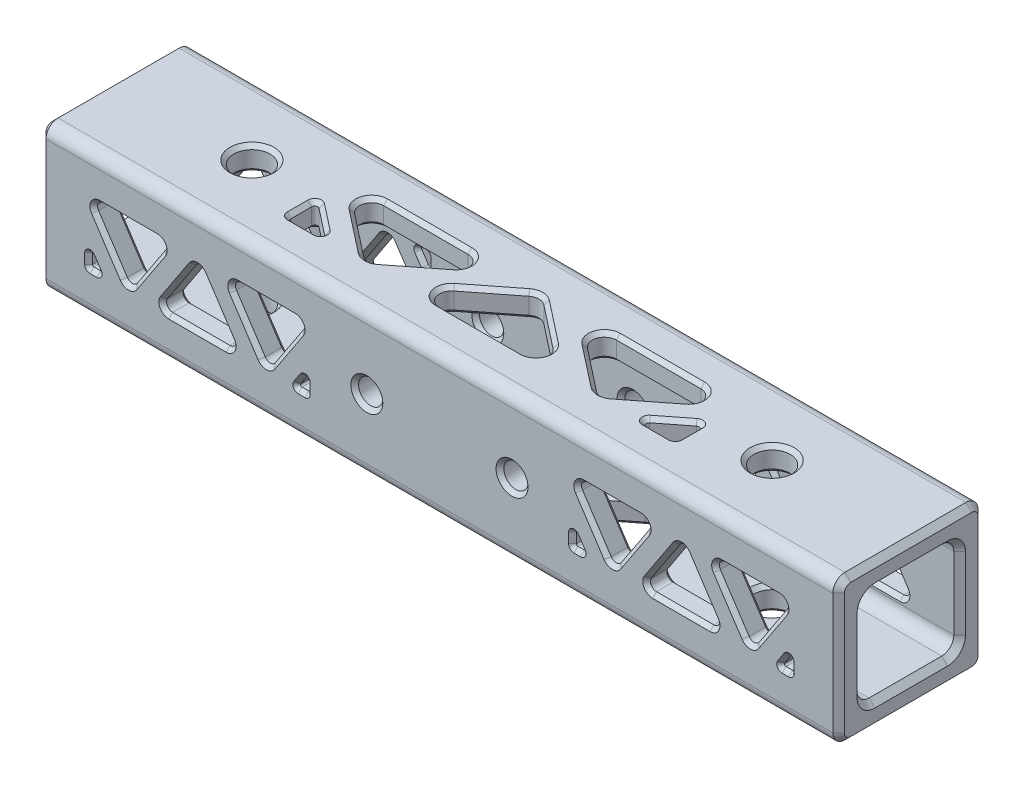
SolidWorks part; units mm, degrees
ref_plane "Front Plane" through (0, 0, 0) normal (0, 0, 1) x (1, 0, 0)
ref_plane "Top Plane" through (0, 0, 0) normal (0, 1, 0) x (1, 0, 0)
ref_plane "Right Plane" through (0, 0, 0) normal (1, 0, 0) x (0, 0, -1)
sketch "Sketch1" plane through (0, 0, 0) normal (1, 0, 0) x (0, 0, -1)
  line L1 (-6.35, -6.35) -> (6.35, -6.35)
  line L2 (-6.35, -6.35) -> (-6.35, 6.35)
  line L3 (-6.35, 6.35) -> (6.35, 6.35)
  line L4 (6.35, -6.35) -> (6.35, 6.35)
  line L5 (-6.35, -6.35) -> (6.35, 6.35) construction
  line L6 (-6.35, 6.35) -> (6.35, -6.35) construction
  line L7 (-9.525, -9.525) -> (9.525, -9.525)
  line L8 (-9.525, -9.525) -> (-9.525, 9.525)
  line L9 (-9.525, 9.525) -> (9.525, 9.525)
  line L10 (9.525, -9.525) -> (9.525, 9.525)
  line L11 (-9.525, -9.525) -> (9.525, 9.525) construction
  line L12 (-9.525, 9.525) -> (9.525, -9.525) construction
  point P0 (0, 0)
  point P6 (0, 0)
  dimension "D1" = 19.05
  dimension "D2" = 12.7
extrude "Boss-Extrude1" add sketch "Sketch1" along normal mid plane 104.775 contours L9 L10 L7 L8
hole_wizard "3/16 (0.1875) Diameter Hole1" positions "Sketch2" profile "Sketch3" hole size "3/16" standard "ANSI Inch" end condition through all
sketch "Sketch2" plane through (0, 9.525, 0) normal (0, 1, 0) x (1, 0, 0)
  line L0 (34.1313, 0) -> (-34.1313, 0) construction
  line L1 (34.1313, 0) -> (52.3875, 0) construction
  line L2 (52.3875, 9.525) -> (52.3875, -9.525) construction
  point P0 (-34.1313, 0)
  point P2 (34.1313, 0)
  dimension "D1" = 18.2562
sketch "Sketch3" plane through (-34.1313, 9.525, 0) normal (1, 0, 0) x (0, 0, 1)
  line L0 (0, 0) -> (0, 19.05)
  line L1 (0, 19.05) -> (2.3812, 19.05)
  line L2 (2.3812, 19.05) -> (2.3812, 0)
  line L5 (2.3812, 0) -> (0, 0)
  line L11 (0, -6.35) -> (0, 107.95) construction
  dimension "Thru Hole Dia." = 4.7625
  dimension "Thru Hole Depth" = 19.05
hole_wizard "1/8 (0.125) Diameter Hole1" positions "Sketch6" profile "Sketch7" hole size "1/8" standard "ANSI Inch" end condition through all
sketch "Sketch6" plane through (0, 0, -9.525) normal (0, 0, -1) x (-1, 0, 0)
  line L2 (-9.525, 0) -> (9.525, 0) construction
  point P18 (9.525, 0)
  point P20 (-9.525, 0)
  dimension "D5" = 19.05
sketch "Sketch7" plane through (9.525, 0, -9.525) normal (1, 0, 0) x (0, 1, 0)
  line L0 (0, 0) -> (0, 19.05)
  line L1 (0, 19.05) -> (1.5875, 19.05)
  line L2 (1.5875, 19.05) -> (1.5875, 0)
  line L5 (1.5875, 0) -> (0, 0)
  line L11 (0, -6.35) -> (0, 107.95) construction
  dimension "Thru Hole Dia." = 3.175
  dimension "Thru Hole Depth" = 19.05
sketch "Sketch8" plane through (0, 9.525, 0) normal (0, 1, 0) x (1, 0, 0)
  line L0 (-34.1313, 0) -> (-34.1313, 9.525) construction
  line L1 (52.3875, 9.525) -> (-52.3875, 9.525) construction
  line L2 (-34.1313, 0) -> (-34.1313, -9.525) construction
  line L3 (52.3875, -9.525) -> (-52.3875, -9.525) construction
  line L4 (-31.75, 0) -> (-31.75, -9.525) construction
  line L5 (-31.75, 0) -> (-31.75, 9.525) construction
  line L6 (34.1313, 0) -> (34.1313, 9.525) construction
  line L7 (34.1313, 0) -> (34.1313, -9.525) construction
  line L8 (31.75, 0) -> (31.75, -9.525) construction
  line L9 (31.75, 0) -> (31.75, 9.525) construction
  line L10 (-25.4, 9.525) -> (-25.4, -9.525) construction
  line L11 (25.4, 9.525) -> (25.4, -9.525) construction
  line L12 (-31.75, 0) -> (-25.4, 0) construction
  line L13 (25.4, 0) -> (31.75, 0) construction
  line L14 (-25.4, 3.9688) -> (25.4, 3.9688) construction
  line L15 (25.4, -3.9688) -> (-25.4, -3.9688) construction
  line L16 (0, -3.9688) -> (0, -9.525) construction
  line L17 (0, 3.9688) -> (0, 9.525) construction
  line L18 (-25.4, -0.0653) -> (-25.4, -3.9688)
  line L19 (-25.4, -3.9688) -> (-20.42, -3.9688)
  line L20 (-20.42, -3.9688) -> (-25.4, -0.0653)
  line L21 (-25.4, 3.9688) -> (-15.2733, -3.9688)
  line L22 (-15.2733, -3.9688) -> (-5.1467, 3.9688)
  line L23 (-5.1467, 3.9688) -> (-25.4, 3.9688)
  line L24 (-10.1267, -3.9688) -> (0, 3.9688)
  line L25 (0, 3.9688) -> (10.1267, -3.9688)
  line L26 (10.1267, -3.9688) -> (-10.1267, -3.9688)
  line L27 (25.4, 3.9688) -> (15.2733, -3.9688)
  line L28 (15.2733, -3.9688) -> (5.1467, 3.9688)
  line L29 (5.1467, 3.9688) -> (25.4, 3.9688)
  line L30 (25.4, -3.9688) -> (25.4, -0.0653)
  line L31 (25.4, -0.0653) -> (20.42, -3.9688)
  line L32 (20.42, -3.9688) -> (25.4, -3.9688)
  line L33 (-22.91, -2.017) -> (-20.9514, 0.4818) construction
  line L34 (22.91, -2.017) -> (20.9514, 0.4818) construction
  line L35 (-5.0633, 0) -> (-7.022, 2.4989) construction
  line L36 (5.0633, 0) -> (7.022, 2.4989) construction
  circle A0 centre (-34.1313, 0) radius 2.3813 construction
  circle A1 centre (34.1313, 0) radius 2.3813 construction
  dimension "D1" = 7.9375
  dimension "D2" = 6.35
  dimension "D3" = 3.175
extrude "Cut-Extrude1" cut sketch "Sketch8" against normal up to next contours L21 L22 L23
sketch "Sketch9" plane through (0, 0, 9.525) normal (0, 0, 1) x (1, 0, 0)
  line L0 (-9.525, 0) -> (-9.525, -9.525) construction
  line L1 (52.3875, -9.525) -> (-52.3875, -9.525) construction
  line L2 (-9.525, 0) -> (-9.525, 9.525) construction
  line L3 (52.3875, 9.525) -> (-52.3875, 9.525) construction
  line L4 (-11.1125, 0) -> (-11.1125, -9.525) construction
  line L5 (-11.1125, 0) -> (-11.1125, 9.525) construction
  line L6 (-46.0375, 3.9688) -> (-46.0375, -3.9687) construction
  line L7 (-46.0375, -3.9687) -> (-17.4625, -3.9688) construction
  line L8 (-11.1125, 0) -> (-17.4625, 0) construction
  line L9 (-46.0375, 0) -> (-52.3875, 0) construction
  line L10 (-52.3875, 9.525) -> (-52.3875, -9.525) construction
  line L11 (-46.0375, 3.9688) -> (-17.4625, 3.9688) construction
  line L12 (-17.4625, -3.9688) -> (-17.4625, 3.9688) construction
  line L13 (-31.75, -3.9687) -> (-31.75, -9.525) construction
  line L14 (-31.75, 3.9687) -> (-31.75, 9.525) construction
  line L15 (9.525, 0) -> (9.525, -9.525) construction
  line L16 (9.525, 0) -> (9.525, 9.525) construction
  line L17 (11.1125, 0) -> (11.1125, -9.525) construction
  line L18 (11.1125, 0) -> (11.1125, 9.525) construction
  line L19 (17.4625, 3.9688) -> (17.4625, -3.9688) construction
  line L20 (17.4625, -3.9688) -> (46.0375, -3.9688) construction
  line L21 (46.0375, -3.9688) -> (46.0375, 3.9688) construction
  line L22 (46.0375, 3.9688) -> (17.4625, 3.9688) construction
  line L23 (11.1125, 0) -> (17.4625, 0) construction
  line L24 (46.0375, 0) -> (52.3875, 0) construction
  line L25 (52.3875, 9.525) -> (52.3875, -9.525) construction
  line L26 (31.75, -3.9688) -> (31.75, -9.525) construction
  line L27 (31.75, 3.9688) -> (31.75, 9.525) construction
  line L28 (-7.9375, 0) -> (-7.9375, -9.525) construction
  line L29 (-7.9375, 0) -> (-7.9375, 9.525) construction
  line L30 (7.9375, 0) -> (7.9375, -9.525) construction
  line L31 (7.9375, 0) -> (7.9375, 9.525) construction
  line L32 (-1.5875, 3.9687) -> (1.5875, 3.9687) construction
  line L33 (1.5875, 3.9687) -> (1.5875, -3.9687) construction
  line L34 (1.5875, -3.9687) -> (-1.5875, -3.9687) construction
  line L35 (-1.5875, -3.9687) -> (-1.5875, 3.9687) construction
  line L36 (-7.9375, 0) -> (-1.5875, 0) construction
  line L37 (1.5875, 0) -> (7.9375, 0) construction
  line L38 (-46.0375, 3.9688) -> (-40.7961, -3.9688)
  line L39 (-40.7961, -3.9688) -> (-35.5548, 3.9688)
  line L40 (-35.5548, 3.9688) -> (-46.0375, 3.9688)
  line L41 (-36.9914, -3.9688) -> (-31.75, 3.9687)
  line L42 (-31.75, 3.9687) -> (-26.5086, -3.9688)
  line L43 (-26.5086, -3.9688) -> (-36.9914, -3.9688)
  line L44 (-17.4625, 3.9688) -> (-22.7039, -3.9688)
  line L45 (-22.7039, -3.9688) -> (-27.9452, 3.9688)
  line L46 (-27.9452, 3.9688) -> (-17.4625, 3.9688)
  line L47 (-22.7039, -3.9688) -> (-22.7039, 3.9688) construction
  line L48 (-31.75, 3.9687) -> (-31.75, -3.9687) construction
  line L49 (-40.7961, -3.9688) -> (-40.7961, 3.9688) construction
  line L50 (-46.0375, -1.7931) -> (-46.0375, -3.9687)
  line L51 (-46.0375, -3.9687) -> (-44.6009, -3.9688)
  line L52 (-44.6009, -3.9688) -> (-46.0375, -1.7931)
  line L53 (-17.4625, -3.9688) -> (-17.4625, -1.7931)
  line L54 (-17.4625, -1.7931) -> (-18.8991, -3.9688)
  line L55 (-18.8991, -3.9688) -> (-17.4625, -3.9688)
  line L56 (-18.1808, -2.8809) -> (-20.8303, -1.1314) construction
  line L57 (-45.3192, -2.8809) -> (-42.6697, -1.1314) construction
  line L58 (-34.3707, 0) -> (-37.0202, 1.7495) construction
  line L59 (-29.1293, 0) -> (-26.4798, 1.7495) construction
  line L60 (17.4625, 3.9688) -> (22.7039, -3.9688)
  line L61 (22.7039, -3.9688) -> (27.9452, 3.9688)
  line L62 (27.9452, 3.9688) -> (17.4625, 3.9688)
  line L63 (26.5086, -3.9688) -> (31.75, 3.9688)
  line L64 (31.75, 3.9688) -> (36.9914, -3.9688)
  line L65 (36.9914, -3.9688) -> (26.5086, -3.9688)
  line L66 (46.0375, 3.9688) -> (40.7961, -3.9688)
  line L67 (40.7961, -3.9688) -> (35.5548, 3.9688)
  line L68 (35.5548, 3.9688) -> (46.0375, 3.9688)
  line L69 (17.4625, -1.7931) -> (17.4625, -3.9688)
  line L70 (17.4625, -3.9688) -> (18.8991, -3.9688)
  line L71 (18.8991, -3.9688) -> (17.4625, -1.7931)
  line L72 (46.0375, -1.7931) -> (46.0375, -3.9688)
  line L73 (46.0375, -3.9688) -> (44.6009, -3.9688)
  line L74 (44.6009, -3.9688) -> (46.0375, -1.7931)
  line L75 (18.1808, -2.8809) -> (20.8303, -1.1314) construction
  line L76 (29.1293, 0) -> (26.4798, 1.7495) construction
  line L77 (34.3707, 0) -> (37.0202, 1.7495) construction
  line L78 (45.3192, -2.8809) -> (42.6697, -1.1314) construction
  circle A0 centre (-9.525, 0) radius 1.5875 construction
  circle A1 centre (9.525, 0) radius 1.5875 construction
  dimension "D1" = 6.35
  dimension "D2" = 7.9375
  dimension "D3" = 7.9375
  dimension "D4" = 6.35
  dimension "D5" = 3.175
extrude "Cut-Extrude2" cut sketch "Sketch9" against normal up to next
ref_axis "Axis1" through (57.6262, 0, 0) along (-1, 0, 0)
pattern_circular "CirPattern1" count 2 over 360 about axis through (57.6262, 0, 0) along (-1, 0, 0) of "Cut-Extrude1"
pattern_circular "CirPattern2" count 2 over 360 about axis through (57.6262, 0, 0) along (-1, 0, 0) of "Cut-Extrude2"
fillet "Fillet1" radius 1.5875 26 edges at (0, -6.35, -6.35) (0, 6.35, -6.35) (0, 6.35, 6.35) (0, -6.35, 6.35) (0, -9.525, -9.525) (0, 9.525, -9.525) (0, -9.525, 9.525) (0, 9.525, 9.525) (25.4, -7.9375, 3.9688) (5.1467, -7.9375, 3.9688) (15.2733, -7.9375, -3.9687) (0, -7.9375, 3.9688) (10.1267, -7.9375, -3.9688) (-10.1267, -7.9375, -3.9688) (-5.1467, -7.9375, 3.9688) (-25.4, -7.9375, 3.9688) (-15.2733, -7.9375, -3.9688) (25.4, 7.9375, -3.9688) (5.1467, 7.9375, -3.9687) (15.2733, 7.9375, 3.9688) (10.1267, 7.9375, 3.9688) (0, 7.9375, -3.9688) (-10.1267, 7.9375, 3.9687) (-5.1467, 7.9375, -3.9688) (-25.4, 7.9375, -3.9687) (-15.2733, 7.9375, 3.9688)
fillet "Fillet4" radius 0.7937 36 edges at (46.0375, 3.9688, 7.9375) (40.7961, -3.9688, 7.9375) (35.5548, 3.9688, 7.9375) (31.75, 3.9688, 7.9375) (36.9914, -3.9688, 7.9375) (26.5086, -3.9688, 7.9375) (17.4625, 3.9688, 7.9375) (27.9452, 3.9688, 7.9375) (22.7039, -3.9688, 7.9375) (-17.4625, 3.9688, 7.9375) (-22.7039, -3.9688, 7.9375) (-27.9452, 3.9688, 7.9375) (-26.5086, -3.9688, 7.9375) (-36.9914, -3.9688, 7.9375) (-31.75, 3.9687, 7.9375) (-35.5548, 3.9688, 7.9375) (-40.7961, -3.9688, 7.9375) (-46.0375, 3.9688, 7.9375) (-40.7961, 3.9688, -7.9375) (-46.0375, -3.9688, -7.9375) (-35.5548, -3.9688, -7.9375) (-36.9914, 3.9688, -7.9375) (-26.5086, 3.9688, -7.9375) (-31.75, -3.9687, -7.9375) (-27.9452, -3.9688, -7.9375) (-17.4625, -3.9688, -7.9375) (-22.7039, 3.9688, -7.9375) (17.4625, -3.9688, -7.9375) (27.9452, -3.9688, -7.9375) (22.7039, 3.9688, -7.9375) (26.5086, 3.9687, -7.9375) (36.9914, 3.9688, -7.9375) (31.75, -3.9688, -7.9375) (35.5548, -3.9688, -7.9375) (40.7961, 3.9688, -7.9375) (46.0375, -3.9688, -7.9375)
fillet "Fillet2" radius 0.3969 12 edges at (20.42, 7.9375, 3.9688) (25.4, 7.9375, 0.0653) (25.4, 7.9375, 3.9688) (-25.4, 7.9375, 0.0653) (-20.42, 7.9375, 3.9688) (-25.4, 7.9375, 3.9688) (-25.4, -7.9375, -0.0653) (-20.42, -7.9375, -3.9688) (-25.4, -7.9375, -3.9688) (20.42, -7.9375, -3.9688) (25.4, -7.9375, -0.0653) (25.4, -7.9375, -3.9688)
fillet "Fillet3" radius 0.1984 24 edges at (-46.0375, 3.9687, -7.9375) (-46.0375, 1.7931, -7.9375) (-44.6009, 3.9688, -7.9375) (-18.8991, 3.9688, -7.9375) (-17.4625, 1.7931, -7.9375) (-17.4625, 3.9688, -7.9375) (17.4625, 3.9688, -7.9375) (17.4625, 1.7931, -7.9375) (18.8991, 3.9688, -7.9375) (44.6009, 3.9688, -7.9375) (46.0375, 3.9688, -7.9375) (46.0375, 1.7931, -7.9375) (46.0375, -3.9688, 7.9375) (46.0375, -1.7931, 7.9375) (44.6009, -3.9688, 7.9375) (18.8991, -3.9688, 7.9375) (17.4625, -1.7931, 7.9375) (17.4625, -3.9688, 7.9375) (-18.8991, -3.9688, 7.9375) (-17.4625, -1.7931, 7.9375) (-17.4625, -3.9688, 7.9375) (-44.6009, -3.9688, 7.9375) (-46.0375, -1.7931, 7.9375) (-46.0375, -3.9687, 7.9375)
chamfer "Chamfer1" distance 0.762 angle 45 32 edges at (-52.3875, 5.885, 5.885) (-52.3875, 6.35, 0) (-52.3875, 5.885, -5.885) (-52.3875, 0, -6.35) (-52.3875, -5.885, -5.885) (-52.3875, -6.35, 0) (-52.3875, -5.885, 5.885) (-52.3875, 0, 6.35) (-52.3875, 9.06, -9.06) (-52.3875, 9.525, 0) (-52.3875, 9.06, 9.06) (-52.3875, 0, 9.525) (-52.3875, -9.06, 9.06) (-52.3875, -9.525, 0) (-52.3875, -9.06, -9.06) (-52.3875, 0, -9.525) (52.3875, 5.885, -5.885) (52.3875, 6.35, 0) (52.3875, 5.885, 5.885) (52.3875, 0, 6.35) (52.3875, -5.885, 5.885) (52.3875, -6.35, 0) (52.3875, -5.885, -5.885) (52.3875, 0, -6.35) (52.3875, -9.06, 9.06) (52.3875, 0, 9.525) (52.3875, 9.06, 9.06) (52.3875, 9.525, 0) (52.3875, 9.06, -9.06) (52.3875, 0, -9.525) (52.3875, -9.06, -9.06) (52.3875, -9.525, 0)
chamfer "Chamfer2" distance 0.508 angle 45 376 edges at (34.1313, 6.35, -2.3812) (34.1313, -6.35, 2.3812) (34.1313, -9.525, 2.3812) (34.1313, 9.525, 2.3813) (15.2733, -9.525, 3.9688) (15.2733, -6.35, 3.9688) (19.0167, -9.525, -1.0347) (19.0167, -6.35, -1.0347) (11.53, -9.525, -1.0347) (11.53, -6.35, -1.0347) (-3.7433, -9.525, 1.0347) (-3.7433, -6.35, 1.0347) (3.7433, -9.525, 1.0347) (3.7433, -6.35, 1.0347) (0, -9.525, -3.9688) (0, -6.35, -3.9688) (-15.2733, -9.525, 3.9688) (-15.2733, -6.35, 3.9688) (-34.1313, 6.35, -2.3812) (-34.1313, -6.35, 2.3812) (-11.53, -9.525, -1.0347) (-11.53, -6.35, -1.0347) (-34.1313, -9.525, 2.3812) (-34.1313, 9.525, 2.3813) (-19.0167, -9.525, -1.0347) (-19.0167, -6.35, -1.0347) (15.2733, 9.525, -3.9688) (15.2733, 6.35, -3.9688) (19.0167, 9.525, 1.0347) (19.0167, 6.35, 1.0347) (11.53, 9.525, 1.0347) (11.53, 6.35, 1.0347) (3.7433, 9.525, -1.0347) (3.7433, 6.35, -1.0347) (0, 9.525, 3.9688) (0, 6.35, 3.9688) (-3.7433, 9.525, -1.0347) (-3.7433, 6.35, -1.0347) (-15.2733, 9.525, -3.9688) (-15.2733, 6.35, -3.9688) (-11.53, 9.525, 1.0347) (-11.53, 6.35, 1.0347) (-19.0167, 9.525, 1.0347) (-19.0167, 6.35, 1.0347) (22.3019, -9.525, 2.8993) (22.3019, -6.35, 2.8993) (8.2448, -9.525, 2.8993) (8.2448, -6.35, 2.8993) (15.2733, -9.525, -3.5392) (15.2733, -6.35, -3.5392) (0, -9.525, 3.5392) (0, -6.35, 3.5392) (7.0286, -9.525, -2.8993) (7.0286, -6.35, -2.8993) (-7.0286, -9.525, -2.8993) (-7.0286, -6.35, -2.8993) (-8.2448, -9.525, 2.8993) (-8.2448, -6.35, 2.8993) (-22.3019, -9.525, 2.8993) (-22.3019, -6.35, 2.8993) (-15.2733, -9.525, -3.5392) (-15.2733, -6.35, -3.5392) (22.3019, 9.525, -2.8993) (22.3019, 6.35, -2.8993) (8.2448, 9.525, -2.8993) (8.2448, 6.35, -2.8993) (15.2733, 9.525, 3.5392) (15.2733, 6.35, 3.5392) (7.0286, 9.525, 2.8993) (7.0286, 6.35, 2.8993) (0, 9.525, -3.5392) (0, 6.35, -3.5392) (-7.0286, 9.525, 2.8993) (-7.0286, 6.35, 2.8993) (-8.2448, 9.525, -2.8993) (-8.2448, 6.35, -2.8993) (-22.3019, 9.525, -2.8993) (-22.3019, 6.35, -2.8993) (-15.2733, 9.525, 3.5392) (-15.2733, 6.35, 3.5392) (7.9375, 0, 6.35) (11.1125, 0, -6.35) (7.9375, 0, -9.525) (7.9375, 0, 9.525) (-38.2507, 0.114, -9.525) (-38.2507, 0.114, -6.35) (-43.3415, 0.114, -9.525) (-43.3415, 0.114, -6.35) (-40.7961, -3.9688, -9.525) (-40.7961, -3.9688, -6.35) (-31.75, 3.9688, -9.525) (-31.75, 3.9688, -6.35) (-34.2954, -0.114, -9.525) (-34.2954, -0.114, -6.35) (-29.2046, -0.114, -9.525) (-29.2046, -0.114, -6.35) (-25.2493, 0.114, -9.525) (-25.2493, 0.114, -6.35) (-22.7039, -3.9688, -9.525) (-22.7039, -3.9688, -6.35) (-20.1585, 0.114, -9.525) (-20.1585, 0.114, -6.35) (20.1585, 0.114, -9.525) (20.1585, 0.114, -6.35) (22.7039, -3.9688, -9.525) (22.7039, -3.9688, -6.35) (25.2493, 0.114, -9.525) (25.2493, 0.114, -6.35) (31.75, 3.9688, -9.525) (-7.9375, 0, -6.35) (31.75, 3.9688, -6.35) (-11.1125, 0, 6.35) (29.2046, -0.114, -9.525) (-11.1125, 0, 9.525) (29.2046, -0.114, -6.35) (-11.1125, 0, -9.525) (34.2954, -0.114, -9.525) (34.2954, -0.114, -6.35) (38.2507, 0.114, -9.525) (38.2507, 0.114, -6.35) (40.7961, -3.9688, -9.525) (40.7961, -3.9688, -6.35) (43.3415, 0.114, -9.525) (43.3415, 0.114, -6.35) (40.7961, 3.9688, 9.525) (40.7961, 3.9688, 6.35) (43.3415, -0.114, 9.525) (43.3415, -0.114, 6.35) (38.2507, -0.114, 9.525) (38.2507, -0.114, 6.35) (29.2046, 0.114, 9.525) (29.2046, 0.114, 6.35) (34.2954, 0.114, 9.525) (34.2954, 0.114, 6.35) (31.75, -3.9688, 9.525) (31.75, -3.9688, 6.35) (20.1585, -0.114, 9.525) (20.1585, -0.114, 6.35) (22.7039, 3.9688, 9.525) (22.7039, 3.9688, 6.35) (25.2493, -0.114, 9.525) (25.2493, -0.114, 6.35) (-22.7039, 3.9688, 9.525) (-22.7039, 3.9688, 6.35) (-20.1585, -0.114, 9.525) (-20.1585, -0.114, 6.35) (-25.2493, -0.114, 9.525) (-25.2493, -0.114, 6.35) (-29.2046, 0.114, 9.525) (-29.2046, 0.114, 6.35) (-31.75, -3.9688, 9.525) (-31.75, -3.9688, 6.35) (-34.2954, 0.114, 9.525) (-34.2954, 0.114, 6.35) (-40.7961, 3.9688, 9.525) (-40.7961, 3.9688, 6.35) (-38.2507, -0.114, 9.525) (-38.2507, -0.114, 6.35) (-43.3415, -0.114, 9.525) (-43.3415, -0.114, 6.35) (-40.7961, 3.322, -9.525) (-40.7961, 3.322, -6.35) (-45.2612, -3.5511, -9.525) (-45.2612, -3.5511, -6.35) (-36.3311, -3.5511, -9.525) (-36.3311, -3.5511, -6.35) (-36.2151, 3.5511, -9.525) (-36.2151, 3.5511, -6.35) (-27.2849, 3.5511, -9.525) (-27.2849, 3.5511, -6.35) (-31.75, -3.322, -9.525) (-31.75, -3.322, -6.35) (-27.1689, -3.5511, -9.525) (-27.1689, -3.5511, -6.35) (-18.2388, -3.5511, -9.525) (-18.2388, -3.5511, -6.35) (-22.7039, 3.322, -9.525) (-22.7039, 3.322, -6.35) (18.2388, -3.5511, -9.525) (18.2388, -3.5511, -6.35) (27.1689, -3.5511, -9.525) (27.1689, -3.5511, -6.35) (22.7039, 3.322, -9.525) (22.7039, 3.322, -6.35) (27.2849, 3.5511, -9.525) (27.2849, 3.5511, -6.35) (36.2151, 3.5511, -9.525) (36.2151, 3.5511, -6.35) (31.75, -3.322, -9.525) (31.75, -3.322, -6.35) (36.3311, -3.5511, -9.525) (36.3311, -3.5511, -6.35) (40.7961, 3.322, -9.525) (40.7961, 3.322, -6.35) (45.2612, -3.5511, -9.525) (45.2612, -3.5511, -6.35) (45.2612, 3.5511, 9.525) (45.2612, 3.5511, 6.35) (40.7961, -3.322, 9.525) (40.7961, -3.322, 6.35) (36.3311, 3.5511, 9.525) (36.3311, 3.5511, 6.35) (31.75, 3.322, 9.525) (31.75, 3.322, 6.35) (36.2151, -3.5511, 9.525) (36.2151, -3.5511, 6.35) (27.2849, -3.5511, 9.525) (27.2849, -3.5511, 6.35) (18.2388, 3.5511, 9.525) (18.2388, 3.5511, 6.35) (27.1689, 3.5511, 9.525) (27.1689, 3.5511, 6.35) (22.7039, -3.322, 9.525) (22.7039, -3.322, 6.35) (-18.2388, 3.5511, 9.525) (-18.2388, 3.5511, 6.35) (-22.7039, -3.322, 9.525) (-22.7039, -3.322, 6.35) (-27.1689, 3.5511, 9.525) (-27.1689, 3.5511, 6.35) (-27.2849, -3.5511, 9.525) (-27.2849, -3.5511, 6.35) (-36.2151, -3.5511, 9.525) (-36.2151, -3.5511, 6.35) (-31.75, 3.322, 9.525) (-31.75, 3.322, 6.35) (-36.3311, 3.5511, 9.525) (-36.3311, 3.5511, 6.35) (-40.7961, -3.322, 9.525) (-40.7961, -3.322, 6.35) (-45.2612, 3.5511, 9.525) (-45.2612, 3.5511, 6.35) (23.2864, 9.525, 3.9688) (23.2864, 6.35, 3.9688) (23.0416, 9.525, 1.9139) (23.0416, 6.35, 1.9139) (25.4, 9.525, 2.2263) (25.4, 6.35, 2.2263) (-25.4, 9.525, 2.2263) (-25.4, 6.35, 2.2263) (-23.0416, 9.525, 1.9139) (-23.0416, 6.35, 1.9139) (-23.2864, 9.525, 3.9688) (-23.2864, 6.35, 3.9688) (-25.4, -9.525, -2.2263) (-25.4, -6.35, -2.2263) (-23.0416, -9.525, -1.9139) (-23.0416, -6.35, -1.9139) (-23.2864, -9.525, -3.9688) (-23.2864, -6.35, -3.9688) (23.2864, -9.525, -3.9688) (23.2864, -6.35, -3.9688) (23.0416, -9.525, -1.9139) (23.0416, -6.35, -1.9139) (25.4, -9.525, -2.2263) (25.4, -6.35, -2.2263) (21.1946, 9.525, 3.7014) (21.1946, 6.35, 3.7014) (25.1768, 9.525, 0.5238) (25.1768, 6.35, 0.5238) (25.2838, 9.525, 3.8525) (25.2838, 6.35, 3.8525) (-25.1768, 9.525, 0.5238) (-25.1768, 6.35, 0.5238) (-21.1946, 9.525, 3.7014) (-21.1946, 6.35, 3.7014) (-25.2838, 9.525, 3.8525) (-25.2838, 6.35, 3.8525) (-25.1768, -9.525, -0.5238) (-25.1768, -6.35, -0.5238) (-21.1946, -9.525, -3.7014) (-21.1946, -6.35, -3.7014) (-25.2838, -9.525, -3.8525) (-25.2838, -6.35, -3.8525) (21.1946, -9.525, -3.7014) (21.1946, -6.35, -3.7014) (25.1768, -9.525, -0.5238) (25.1768, -6.35, -0.5238) (25.2838, -9.525, -3.8525) (25.2838, -6.35, -3.8525) (-45.4044, 3.9687, -9.525) (-45.4044, 3.9687, -6.35) (-46.0375, 3.112, -9.525) (-46.0375, 3.112, -6.35) (-45.2388, 3.0027, -9.525) (-45.2388, 3.0027, -6.35) (-18.0956, 3.9688, -9.525) (-18.0956, 3.9688, -6.35) (-18.2612, 3.0027, -9.525) (-18.2612, 3.0027, -6.35) (-17.4625, 3.112, -9.525) (-17.4625, 3.112, -6.35) (18.0956, 3.9688, -9.525) (18.0956, 3.9688, -6.35) (17.4625, 3.112, -9.525) (17.4625, 3.112, -6.35) (18.2612, 3.0027, -9.525) (18.2612, 3.0027, -6.35) (45.4044, 3.9688, -9.525) (45.4044, 3.9688, -6.35) (45.2388, 3.0027, -9.525) (45.2388, 3.0027, -6.35) (46.0375, 3.112, -9.525) (46.0375, 3.112, -6.35) (46.0375, -3.112, 9.525) (46.0375, -3.112, 6.35) (45.4044, -3.9688, 9.525) (45.4044, -3.9688, 6.35) (45.2388, -3.0027, 9.525) (45.2388, -3.0027, 6.35) (18.2612, -3.0027, 9.525) (18.2612, -3.0027, 6.35) (18.0956, -3.9688, 9.525) (18.0956, -3.9688, 6.35) (17.4625, -3.112, 9.525) (17.4625, -3.112, 6.35) (-18.0956, -3.9688, 9.525) (-18.0956, -3.9688, 6.35) (-18.2612, -3.0027, 9.525) (-18.2612, -3.0027, 6.35) (-17.4625, -3.112, 9.525) (-17.4625, -3.112, 6.35) (-45.2388, -3.0027, 9.525) (-45.2388, -3.0027, 6.35) (-45.4044, -3.9687, 9.525) (-45.4044, -3.9687, 6.35) (-46.0375, -3.112, 9.525) (-46.0375, -3.112, 6.35) (-45.9794, 3.9106, -9.525) (-45.9794, 3.9106, -6.35) (-45.8961, 2.2637, -9.525) (-45.8961, 2.2637, -6.35) (-44.795, 3.8643, -9.525) (-44.795, 3.8643, -6.35) (-18.705, 3.8643, -9.525) (-18.705, 3.8643, -6.35) (-17.6039, 2.2637, -9.525) (-17.6039, 2.2637, -6.35) (-17.5206, 3.9106, -9.525) (-17.5206, 3.9106, -6.35) (17.5206, 3.9106, -9.525) (17.5206, 3.9106, -6.35) (17.6039, 2.2637, -9.525) (17.6039, 2.2637, -6.35) (18.705, 3.8643, -9.525) (18.705, 3.8643, -6.35) (44.795, 3.8643, -9.525) (44.795, 3.8643, -6.35) (45.9794, 3.9106, -9.525) (45.9794, 3.9106, -6.35) (45.8961, 2.2637, -9.525) (45.8961, 2.2637, -6.35) (45.9794, -3.9106, 9.525) (45.9794, -3.9106, 6.35) (45.8961, -2.2637, 9.525) (45.8961, -2.2637, 6.35) (44.795, -3.8643, 9.525) (44.795, -3.8643, 6.35) (18.705, -3.8643, 9.525) (18.705, -3.8643, 6.35) (17.6039, -2.2637, 9.525) (17.6039, -2.2637, 6.35) (17.5206, -3.9106, 9.525) (17.5206, -3.9106, 6.35) (-18.705, -3.8643, 9.525) (-18.705, -3.8643, 6.35) (-17.6039, -2.2637, 9.525) (-17.6039, -2.2637, 6.35) (-17.5206, -3.9106, 9.525) (-17.5206, -3.9106, 6.35) (-44.795, -3.8643, 9.525) (-44.795, -3.8643, 6.35) (-45.8961, -2.2637, 9.525) (-45.8961, -2.2637, 6.35) (-45.9794, -3.9106, 9.525) (-45.9794, -3.9106, 6.35)
